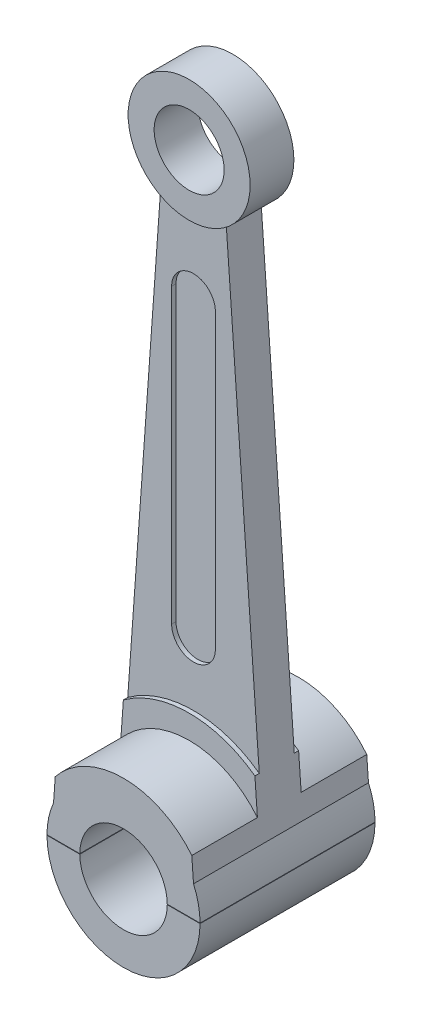
SolidWorks part; units mm, degrees
ref_plane "Front Plane" through (0, 0, 0) normal (0, 0, 1) x (1, 0, 0)
ref_plane "Top Plane" through (0, 0, 0) normal (0, 1, 0) x (1, 0, 0)
ref_plane "Right Plane" through (0, 0, 0) normal (1, 0, 0) x (0, 0, -1)
sketch "Sketch1" plane through (0, 0, 0) normal (0, 0, 1) x (1, 0, 0)
  line L0 (0, 13.69) -> (0, 0) construction
  line L1 (-0.75, 12.5138) -> (-1.65, 1.9311)
  line L2 (0.75, 12.5138) -> (1.65, 1.9311)
  line L3 (0, 10.69) -> (0, 4) construction
  line L4 (0.5, 10.69) -> (0.5, 4)
  line L5 (-0.5, 10.69) -> (-0.5, 4)
  circle A0 centre (0, 0) radius 1
  circle A1 centre (0, 0) radius 2.54
  circle A2 centre (0, 13.69) radius 1.395
  circle A3 centre (0, 13.69) radius 0.8
  arc A4 (0.5, 10.69) -> (-0.5, 10.69) centre (0, 10.69) ccw
  arc A5 (-0.5, 4) -> (0.5, 4) centre (0, 4) ccw
  point P13 (0, 7.345)
  dimension "D1" = 2.79
  dimension "D2" = 1.6
  dimension "D3" = 5.08
  dimension "D4" = 2
  dimension "D7" = 0.5
  dimension "D5" = 13.69
  dimension "D6" = 1.5
  dimension "D8" = 3
  dimension "D9" = 4
  dimension "D10" = 3.3
extrude "Boss-Extrude1" add sketch "Sketch1" along normal mid plane 1 contours A2 A3 | A1 A0 region at (-0.6518, 14.8786, 0) region at (0, 2.4682, 0)
extrude "Boss-Extrude2" add sketch "Sketch1<3>" along normal mid plane 0.8 contours A2 L1 A1 L2 A5 L5 A4 L4 region at (0, 12.1841, 0)
sketch "Sketch1<3>" plane through (0, 0, 0) normal (0, 0, 1) x (1, 0, 0) same geometry as "Sketch1"
extrude "Boss-Extrude3" add sketch "Sketch1<4>" along normal mid plane 0.6 contours L5 A5 L4 A4
sketch "Sketch1<4>" plane through (0, 0, 0) normal (0, 0, 1) x (1, 0, 0) same geometry as "Sketch1"
sketch "Sketch2" plane through (0, 0, 0.5) normal (0, 0, 1) x (1, 0, 0)
  circle A0 centre (0, 0) radius 1 construction
  circle A1 centre (0, 0) radius 1
  circle A2 centre (0, 0) radius 2
  dimension "D1" = 4
extrude "Boss-Extrude4" add sketch "Sketch2" along normal blind 1.5 and the other way blind 2.5
sketch "Sketch3" plane through (0, 0, 0) normal (0, 0, 1) x (1, 0, 0)
  line L0 (-0.75, 12.5138) -> (-3.0406, 1.7334)
  line L1 (0.75, 12.5138) -> (3.0406, 1.7334)
  line L2 (1.6, 0.7089) -> (0.75, 12.5138)
  line L3 (-1.6, 0.7089) -> (-0.75, 12.5138)
  arc A0 (1.6, 0.7089) -> (-1.6, 0.7089) centre (0, 0) cw
  arc A1 (-3.0406, 1.7334) -> (3.0406, 1.7334) centre (0, 0) ccw
  dimension "D1" = 1.75
  dimension "D3" = 3.5
  dimension "D2" = 3.2
extrude "Cut-Extrude1" cut sketch "Sketch3" against normal through all both and the other way through all
sketch "Sketch4" plane through (0, 0, 0) normal (0, 0, 1) x (1, 0, 0)
  line L1 (-2.9401, -0.005) -> (2.9401, -0.005)
  line L2 (-2.9401, -0.005) -> (-2.9401, 0.005)
  line L3 (-2.9401, 0.005) -> (2.9401, 0.005)
  line L4 (2.9401, -0.005) -> (2.9401, 0.005)
  line L5 (-2.9401, -0.005) -> (2.9401, 0.005) construction
  line L6 (-2.9401, 0.005) -> (2.9401, -0.005) construction
  point P0 (0, 0)
  dimension "D1" = 0.01
extrude "Cut-Extrude2" cut sketch "Sketch4" against normal through all both and the other way through all
